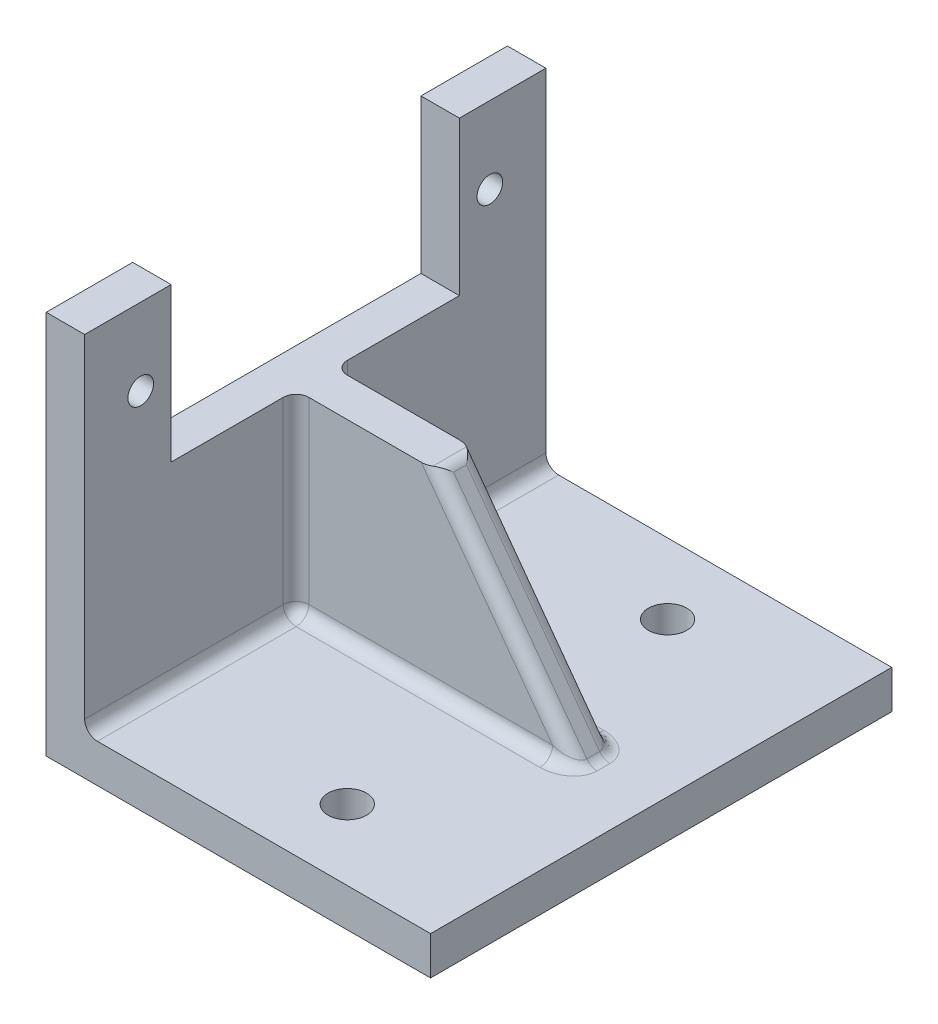
SolidWorks part; units mm, degrees
ref_plane "Front Plane" through (0, 0, 0) normal (0, 0, 1) x (1, 0, 0)
ref_plane "Top Plane" through (0, 0, 0) normal (0, 1, 0) x (1, 0, 0)
ref_plane "Right Plane" through (0, 0, 0) normal (1, 0, 0) x (0, 0, -1)
sketch "Sketch1" plane through (0, 0, 0) normal (0, 0, 1) x (1, 0, 0)
  line L0 (0, 30) -> (0, 0)
  line L1 (0, 0) -> (30, 0)
extrude "Extrude-Thin1" add sketch "Sketch1" along normal mid plane 36 thin thin type one direction reverse wall 3
sketch "Sketch2" plane through (3, 0, 0) normal (1, 0, 0) x (0, 0, -1)
  line L0 (-18, 30) -> (18, 30) construction
  line L1 (-11.25, 18) -> (11.25, 18)
  line L2 (-11.25, 18) -> (-11.25, 30)
  line L3 (-11.25, 30) -> (11.25, 30)
  line L4 (11.25, 18) -> (11.25, 30)
  line L5 (-11.25, 18) -> (11.25, 30) construction
  line L6 (-11.25, 30) -> (11.25, 18) construction
  line L8 (-18, 30) -> (-18, 3) construction
  point P0 (0, 24)
  dimension "D1" = 22.5
  dimension "D2" = 12
  dimension "D3" = 6.75
extrude "Cut-Extrude1" cut sketch "Sketch2" against normal through all
sketch "Sketch3" plane through (3, 0, 0) normal (1, 0, 0) x (0, 0, -1)
  line L0 (-18, 30) -> (-11.25, 30) construction
  line L1 (-18, 30) -> (-18, 3) construction
  line L4 (11.25, 30) -> (18, 30) construction
  circle A0 centre (13.625, 24) radius 1
  circle A1 centre (-13.625, 24) radius 1
  dimension "D1" = 2
  dimension "D2" = 2
  dimension "D3" = 27.25
  dimension "D4" = 6
  dimension "D5" = 4.375
  dimension "D6" = 6
extrude "Cut-Extrude2" cut sketch "Sketch3" against normal blind 10
sketch "Sketch4" plane through (0, 3, 0) normal (0, 1, 0) x (1, 0, 0)
  line L0 (3, -18) -> (3, 18) construction
  line L1 (3, 1.5) -> (25, 1.5)
  line L2 (3, 1.5) -> (3, -1.5)
  line L3 (3, -1.5) -> (25, -1.5)
  line L4 (25, 1.5) -> (25, -1.5)
  line L5 (3, -18) -> (30, -18) construction
  line L7 (30, -18) -> (30, 18) construction
  dimension "D1" = 3
  dimension "D2" = 16.5
  dimension "D3" = 5
extrude "Boss-Extrude1" add sketch "Sketch4" along normal blind 15
sketch "Sketch5" plane through (0, 0, 1.5) normal (0, 0, 1) x (1, 0, 0)
  line L0 (14, 18) -> (25, 3)
  line L1 (3, 18) -> (25, 18) construction
extrude "Cut-Extrude3" cut sketch "Sketch5" against normal blind 15 and the other way through all
fillet "Fillet1" radius 1 10 edges at (3, 3, -9.75) (3, 3, 9.75) (3, 10.5, 1.5) (3, 10.5, -1.5) (14, 3, -1.5) (25, 3, 0) (14, 3, 1.5) (14, 18, 0) (19.5, 10.5, -1.5) (19.5, 10.5, 1.5)
sketch "Sketch6" plane through (0, 3, 0) normal (0, 1, 0) x (1, 0, 0)
  line L0 (4, 18) -> (30, 18) construction
  line L1 (30, -18) -> (30, 18) construction
  circle A0 centre (18, 12.5) radius 1.5
  circle A1 centre (18, -12.5) radius 1.5
  dimension "D1" = 25
  dimension "D2" = 3
  dimension "D3" = 5.5
  dimension "D4" = 12
extrude "Cut-Extrude4" cut sketch "Sketch6" against normal blind 15
